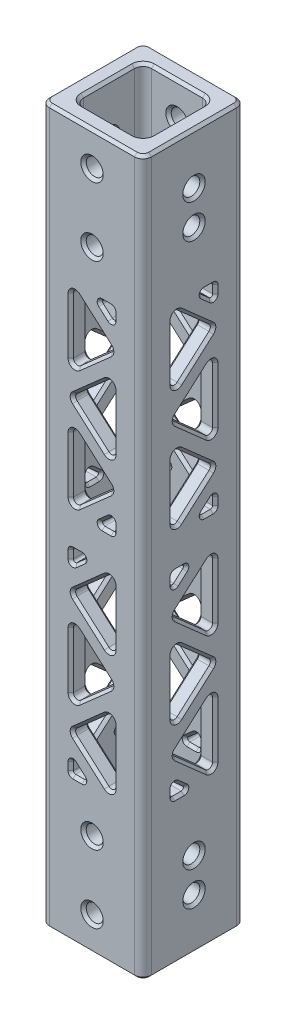
SolidWorks part; units mm, degrees
note: '?' marks a value the reader was unsure of.
ref_plane "Front Plane" through (0, 0, 0) normal (0, 0, 1) x (1, 0, 0)
ref_plane "Top Plane" through (0, 0, 0) normal (0, 1, 0) x (1, 0, 0)
ref_plane "Right Plane" through (0, 0, 0) normal (1, 0, 0) x (0, 0, -1)
sketch "Sketch1" plane through (0, 0, 0) normal (0, 1, 0) x (1, 0, 0)
  line L1 (-9.525, -9.525) -> (9.525, -9.525)
  line L2 (-9.525, -9.525) -> (-9.525, 9.525)
  line L3 (-9.525, 9.525) -> (9.525, 9.525)
  line L4 (9.525, -9.525) -> (9.525, 9.525)
  line L5 (-9.525, -9.525) -> (9.525, 9.525) construction
  line L6 (-9.525, 9.525) -> (9.525, -9.525) construction
  line L7 (-6.35, -6.35) -> (6.35, -6.35)
  line L8 (-6.35, -6.35) -> (-6.35, 6.35)
  line L9 (-6.35, 6.35) -> (6.35, 6.35)
  line L10 (6.35, -6.35) -> (6.35, 6.35)
  line L11 (-6.35, -6.35) -> (6.35, 6.35) construction
  line L12 (-6.35, 6.35) -> (6.35, -6.35) construction
  point P0 (0, 0)
  point P6 (0, 0)
  dimension "D1" = 19.05
  dimension "D2" = 19.05
  dimension "D3" = 12.7
extrude "Boss-Extrude1" add sketch "Sketch1" along normal mid plane 133.35 contours L3 L4 L1 L2
hole_wizard "1/8 (0.125) Diameter Hole1" positions "Sketch8" profile "Sketch9" hole size "1/8" standard "ANSI Inch" end condition through all
sketch "Sketch8" plane through (-9.525, 0, 0) normal (-1, 0, 0) x (0, 0, 1)
  line L2 (0, 57.15) -> (0, 66.675) construction
  line L3 (-9.525, 66.675) -> (9.525, 66.675) construction
  point P0 (0, 57.15)
  point P2 (0, 50.8)
  dimension "D1" = 6.35
  dimension "D2" = 9.525
sketch "Sketch9" plane through (-9.525, 57.15, 0) normal (0, 1, 0) x (0, 0, 1)
  line L0 (0, 0) -> (0, 19.05)
  line L1 (0, 19.05) -> (1.5875, 19.05)
  line L2 (1.5875, 19.05) -> (1.5875, 0)
  line L5 (1.5875, 0) -> (0, 0)
  line L11 (0, -6.35) -> (0, 107.95) construction
  dimension "Thru Hole Dia." = 3.175
  dimension "Thru Hole Depth" = 19.05
hole_wizard "1/8 (0.125) Diameter Hole2" positions "Sketch10" profile "Sketch11" hole size "1/8" standard "ANSI Inch" end condition through all
sketch "Sketch10" plane through (9.525, 0, 0) normal (1, 0, 0) x (0, 0, -1)
  line L0 (0, -66.675) -> (0, -57.15) construction
  line L1 (-9.525, -66.675) -> (9.525, -66.675) construction
  point P0 (0, -50.8)
  point P2 (0, -57.15)
  dimension "D1" = 6.35
  dimension "D2" = 9.525
sketch "Sketch11" plane through (9.525, -50.8, 0) normal (0, 1, 0) x (0, 0, -1)
  line L0 (0, 0) -> (0, 19.05)
  line L1 (0, 19.05) -> (1.5875, 19.05)
  line L2 (1.5875, 19.05) -> (1.5875, 0)
  line L5 (1.5875, 0) -> (0, 0)
  line L11 (0, -6.35) -> (0, 107.95) construction
  dimension "Thru Hole Dia." = 3.175
  dimension "Thru Hole Depth" = 19.05
hole_wizard "1/8 (0.125) Diameter Hole3" positions "Sketch16" profile "Sketch17" hole size "1/8" standard "ANSI Inch" end condition through all
sketch "Sketch16" plane through (0, 0, 9.525) normal (0, 0, 1) x (1, 0, 0)
  line L0 (0, -60.325) -> (0, -66.675) construction
  line L1 (-9.525, -66.675) -> (9.525, -66.675) construction
  line L3 (0, -47.625) -> (0, -60.325) construction
  line L5 (0, 60.325) -> (0, 66.675) construction
  line L6 (-9.525, 66.675) -> (9.525, 66.675) construction
  line L8 (0, 47.625) -> (0, 60.325) construction
  point P0 (0, 60.325)
  point P2 (0, 47.625)
  point P4 (0, -47.625)
  point P6 (0, -60.325)
  dimension "D1" = 6.35
  dimension "D2" = 12.7
sketch "Sketch17" plane through (0, 60.325, 9.525) normal (1, 0, 0) x (0, -1, 0)
  line L0 (0, 0) -> (0, 19.05)
  line L1 (0, 19.05) -> (1.5875, 19.05)
  line L2 (1.5875, 19.05) -> (1.5875, 0)
  line L5 (1.5875, 0) -> (0, 0)
  line L11 (0, -6.35) -> (0, 107.95) construction
  dimension "Thru Hole Dia." = 3.175
  dimension "Thru Hole Depth" = 19.05
sketch "Sketch15" plane through (0, 0, 0) normal (0, 0, 1) x (1, 0, 0)
  line L0 (-3.9687, 39.6875) -> (3.9688, 39.6875) construction
  line L3 (3.9688, 39.6875) -> (3.9687, -39.6875) construction
  line L8 (3.9687, -39.6875) -> (-3.9687, -39.6875) construction
  line L11 (-3.9687, -39.6875) -> (-3.9687, 39.6875) construction
  line L12 (0, -46.0375) -> (0, -39.6875) construction
  line L13 (0, 46.0375) -> (0, 39.6875) construction
  line L23 (-3.9688, 3.175) -> (3.9688, 3.175) construction
  line L24 (-3.9688, -3.175) -> (3.9688, -3.175) construction
  line L28 (0, -3.175) -> (0, 3.175) construction
  line L30 (-3.9687, 39.6875) -> (-0.8276, 39.6875)
  line L31 (-0.8276, 39.6875) -> (-3.9688, 36.9133)
  line L32 (-3.9688, 36.9133) -> (-3.9687, 39.6875)
  line L36 (-3.9688, 32.6774) -> (3.9688, 39.6875)
  line L37 (3.9688, 39.6875) -> (3.9687, 25.6672)
  line L38 (3.9687, 25.6672) -> (-3.9688, 32.6774)
  line L39 (0, 36.1824) -> (-2.1017, 38.5622) construction
  line L45 (-3.9688, 28.4414) -> (3.9688, 21.4313)
  line L49 (3.9688, 21.4313) -> (-3.9688, 14.4211)
  line L53 (-3.9688, 14.4211) -> (-3.9688, 28.4414)
  line L60 (0, 29.1723) -> (-2.1017, 26.7925) construction
  line L64 (-3.9687, 10.1851) -> (3.9687, 17.1953)
  line L68 (3.9687, 17.1953) -> (3.9688, 3.175)
  line L69 (3.9688, 3.175) -> (-3.9687, 10.1851)
  line L70 (0, 13.6902) -> (-2.1017, 16.07) construction
  line L74 (-3.9688, 3.175) -> (-0.8276, 3.175)
  line L78 (-0.8276, 3.175) -> (-3.9688, 5.9492)
  line L88 (0.8276, -3.175) -> (3.9688, -3.175)
  line L89 (-3.9688, -3.175) -> (3.9687, -10.1851)
  line L90 (3.9687, -10.1851) -> (-3.9688, -17.1953)
  line L91 (-3.9688, -17.1953) -> (-3.9688, -3.175)
  line L92 (3.9688, -3.175) -> (3.9687, -5.9492)
  line L93 (-3.9687, -21.4313) -> (3.9688, -14.4211)
  line L94 (3.9688, -14.4211) -> (3.9687, -28.4414)
  line L95 (3.9687, -28.4414) -> (-3.9687, -21.4313)
  line L96 (0, -17.9262) -> (-2.1017, -15.5464) construction
  line L97 (-3.9687, -39.6875) -> (3.9687, -32.6774)
  line L98 (3.9687, -32.6774) -> (-3.9687, -25.6672)
  line L99 (-3.9687, -25.6672) -> (-3.9687, -39.6875)
  line L100 (0, -29.1723) -> (2.1017, -26.7925) construction
  line L101 (0.8276, -39.6875) -> (3.9687, -39.6875)
  line L102 (3.9687, -39.6875) -> (3.9688, -36.9133)
  line L103 (3.9688, -36.9133) -> (0.8276, -39.6875)
  line L104 (2.3982, -38.3004) -> (0.2964, -35.9206) construction
  line L105 (-3.9688, 5.9492) -> (-3.9688, 3.175)
  line L106 (-2.3982, 4.5621) -> (-0.2964, 6.9419) construction
  line L107 (3.9687, -5.9492) -> (0.8276, -3.175)
  line L108 (2.3982, -4.5621) -> (0.2964, -6.9419) construction
  circle A7 centre (0, -47.625) radius 1.5875 construction
  circle A8 centre (0, 47.625) radius 1.5875 construction
  dimension "D3" = 3.175
  dimension "D1" = 7.9375
  dimension "D2" = 6.35
  dimension "D4" = 6.35
extrude "Cut-Extrude1" cut sketch "Sketch15" against normal up to next
ref_axis "Axis2" through (0, -73.3425, 0) along (0, 1, 0)?
pattern_circular "CirPattern2" count 4 over 360 about axis through (0, 0, 0) along (0, 1, 0) of "Cut-Extrude1"
fillet "Fillet1" radius 1.5875 8 edges at (9.525, 0, -9.525) (9.525, 0, 9.525) (-9.525, 0, -9.525) (-9.525, 0, 9.525) (6.35, 0, -6.35) (6.35, 0, 6.35) (-6.35, 0, 6.35) (-6.35, 0, -6.35)
fillet "Fillet2" radius 0.7937 39 edges at (3.9688, -39.6875, 7.9375) (-3.9687, -28.4414, 7.9375) (3.9687, -21.4313, 7.9375) (-3.9688, -14.4211, 7.9375) (3.9688, -17.1953, 7.9375) (-3.9688, 3.175, 7.9375) (3.9688, 28.4414, 7.9375) (-3.9688, 21.4313, 7.9375) (3.9688, 32.6774, 7.9375) (7.9375, -32.6774, 3.9687) (7.9375, -39.6875, -3.9688) (7.9375, -25.6672, -3.9688) (7.9375, -14.4211, 3.9687) (7.9375, -3.175, -3.9688) (7.9375, -10.1851, 3.9687) (7.9375, 3.175, 3.9687) (7.9375, 17.1953, 3.9687) (7.9375, 21.4313, 3.9687) (7.9375, 32.6774, -3.9688) (3.9688, -32.6774, -7.9375) (-3.9687, -25.6672, -7.9375) (3.9687, -28.4414, -7.9375) (-3.9687, -21.4313, -7.9375) (3.9687, -10.1851, -7.9375) (3.9688, 3.175, -7.9375) (-3.9687, 14.4211, -7.9375) (3.9687, 21.4312, -7.9375) (3.9688, 39.6875, -7.9375) (-7.9375, -39.6875, 3.9688) (-7.9375, -25.6672, 3.9688) (-7.9375, -28.4414, -3.9687) (-7.9375, -21.4313, 3.9688) (-7.9375, -10.1851, -3.9687) (-7.9375, 3.175, -3.9687) (-7.9375, 17.1953, -3.9687) (-7.9375, 14.4211, 3.9688) (-7.9375, 21.4313, -3.9687) (-7.9375, 28.4414, 3.9688) (-7.9375, 39.6875, -3.9687)
fillet "Fillet3" radius 0.3969 48 edges at (0.8276, -39.6875, -7.9375) (3.9688, -36.9133, -7.9375) (3.9687, -39.6875, -7.9375) (-3.9688, 36.9133, -7.9375) (-0.8276, 39.6875, -7.9375) (-3.9687, 39.6875, -7.9375) (7.9375, -39.6875, 0.8276) (7.9375, -39.6875, 3.9687) (7.9375, -36.9133, 3.9687) (7.9375, 36.9133, -3.9688) (7.9375, 39.6875, -0.8276) (7.9375, 39.6875, -3.9688) (-0.8276, -39.6875, 7.9375) (-3.9688, -36.9133, 7.9375) (-3.9687, -39.6875, 7.9375) (3.9688, 36.9133, 7.9375) (0.8276, 39.6875, 7.9375) (3.9687, 39.6875, 7.9375) (-7.9375, -39.6875, -0.8276) (-7.9375, -39.6875, -3.9687) (-7.9375, -36.9133, -3.9687) (-7.9375, 36.9133, 3.9688) (-7.9375, 39.6875, 3.9688) (-7.9375, 39.6875, 0.8276) (7.9375, -3.175, 3.9687) (7.9375, -3.175, 0.8276) (7.9375, -5.9492, 3.9687) (7.9375, 3.175, -3.9688) (7.9375, 5.9492, -3.9688) (7.9375, 3.175, -0.8276) (3.9688, -5.9492, -7.9375) (0.8276, -3.175, -7.9375) (3.9688, -3.175, -7.9375) (-3.9688, 3.175, -7.9375) (-3.9688, 5.9492, -7.9375) (-0.8276, 3.175, -7.9375) (-7.9375, 3.175, 0.8276) (-7.9375, 5.9492, 3.9688) (-7.9375, 3.175, 3.9688) (-7.9375, -5.9492, -3.9687) (-7.9375, -3.175, -0.8276) (-7.9375, -3.175, -3.9687) (-3.9688, -3.175, 7.9375) (-0.8276, -3.175, 7.9375) (-3.9687, -5.9492, 7.9375) (0.8276, 3.175, 7.9375) (3.9688, 5.9492, 7.9375) (3.9688, 3.175, 7.9375)
chamfer "Chamfer2" distance 0.508 angle 45 544 edges at (9.525, 3.175, -2.7242) (6.35, 3.175, -2.7242) (9.525, 4.3205, -3.9688) (6.35, 4.3205, -3.9688) (9.525, 4.618, -2.4615) (6.35, 4.618, -2.4615) (3.9688, -4.3205, -9.525) (3.9688, -4.3205, -6.35) (2.4615, -4.618, -9.525) (2.4615, -4.618, -6.35) (2.7242, -3.175, -9.525) (2.7242, -3.175, -6.35) (-2.7242, 3.175, -9.525) (-2.7242, 3.175, -6.35) (-3.9688, 4.3205, -9.525) (-3.9688, 4.3205, -6.35) (-2.4615, 4.618, -9.525) (-2.4615, 4.618, -6.35) (-9.525, 4.618, 2.4615) (-6.35, 4.618, 2.4615) (-9.525, 3.175, 2.7242) (-6.35, 3.175, 2.7242) (-9.525, 4.3205, 3.9688) (-6.35, 4.3205, 3.9688) (-9.525, -4.3205, -3.9687) (-6.35, -4.3205, -3.9687) (-9.525, -4.618, -2.4615) (-6.35, -4.618, -2.4615) (-9.525, -3.175, -2.7242) (-6.35, -3.175, -2.7242) (-2.7242, -3.175, 9.525) (-2.7242, -3.175, 6.35) (-3.9688, -4.3205, 9.525) (-3.9688, -4.3205, 6.35) (-2.4615, -4.618, 9.525) (-2.4615, -4.618, 6.35) (2.4615, 4.618, 9.525) (2.4615, 4.618, 6.35) (2.7242, 3.175, 9.525) (2.7242, 3.175, 6.35) (3.9688, 4.3205, 9.525) (3.9688, 4.3205, 6.35) (2.7242, -39.6875, -9.525) (2.7242, -39.6875, -6.35) (2.4615, -38.2445, -9.525) (2.4615, -38.2445, -6.35) (3.9688, -38.542, -9.525) (3.9688, -38.542, -6.35) (-2.4615, 38.2445, -9.525) (-2.4615, 38.2445, -6.35) (-3.9688, 38.542, -9.525) (-3.9688, 38.542, -6.35) (-2.7242, 39.6875, -9.525) (-2.7242, 39.6875, -6.35) (9.525, -39.6875, 2.7242) (6.35, -39.6875, 2.7242) (9.525, -38.2445, 2.4615) (6.35, -38.2445, 2.4615) (9.525, -38.542, 3.9687) (6.35, -38.542, 3.9687) (9.525, 38.2445, -2.4615) (6.35, 38.2445, -2.4615) (9.525, 38.542, -3.9688) (6.35, 38.542, -3.9688) (9.525, 39.6875, -2.7242) (6.35, 39.6875, -2.7242) (-2.7242, -39.6875, 9.525) (-2.7242, -39.6875, 6.35) (-2.4615, -38.2445, 9.525) (-2.4615, -38.2445, 6.35) (-3.9688, -38.542, 9.525) (-3.9688, -38.542, 6.35) (2.4615, 38.2445, 9.525) (2.4615, 38.2445, 6.35) (3.9688, 38.542, 9.525) (3.9688, 38.542, 6.35) (2.7242, 39.6875, 9.525) (2.7242, 39.6875, 6.35) (-9.525, -39.6875, -2.7242) (-6.35, -39.6875, -2.7242) (-9.525, -38.2445, -2.4615) (-6.35, -38.2445, -2.4615) (-9.525, -38.542, -3.9687) (-6.35, -38.542, -3.9687) (-9.525, 38.2445, 2.4615) (-6.35, 38.2445, 2.4615) (-9.525, 38.542, 3.9688) (-6.35, 38.542, 3.9688) (-9.525, 39.6875, 2.7242) (-6.35, 39.6875, 2.7242) (6.35, -3.2912, 3.8525) (9.525, -3.2912, 3.8525) (6.35, -3.4314, 1.5053) (9.525, -3.4314, 1.5053) (6.35, -5.431, 3.735) (9.525, -5.431, 3.735) (6.35, 3.2912, -3.8525) (9.525, 3.2912, -3.8525) (6.35, 5.431, -3.735) (9.525, 5.431, -3.735) (6.35, 3.4314, -1.5053) (9.525, 3.4314, -1.5053) (3.735, -5.431, -6.35) (3.735, -5.431, -9.525) (1.5053, -3.4314, -6.35) (1.5053, -3.4314, -9.525) (3.8525, -3.2912, -6.35) (3.8525, -3.2912, -9.525) (-3.8525, 3.2912, -6.35) (-3.8525, 3.2912, -9.525) (-3.735, 5.431, -6.35) (-3.735, 5.431, -9.525) (-1.5053, 3.4314, -6.35) (-1.5053, 3.4314, -9.525) (-6.35, 3.4314, 1.5053) (-9.525, 3.4314, 1.5053) (-6.35, 5.431, 3.735) (-9.525, 5.431, 3.735) (-6.35, 3.2912, 3.8525) (-9.525, 3.2912, 3.8525) (-6.35, -5.431, -3.735) (-9.525, -5.431, -3.735) (-6.35, -3.4314, -1.5053) (-9.525, -3.4314, -1.5053) (-6.35, -3.2912, -3.8525) (-9.525, -3.2912, -3.8525) (-3.8525, -3.2912, 6.35) (-3.8525, -3.2912, 9.525) (-1.5053, -3.4314, 6.35) (-1.5053, -3.4314, 9.525) (-3.735, -5.431, 6.35) (-3.735, -5.431, 9.525) (1.5053, 3.4314, 6.35) (1.5053, 3.4314, 9.525) (3.735, 5.431, 6.35) (3.735, 5.431, 9.525) (3.8525, 3.2912, 6.35) (3.8525, 3.2912, 9.525) (1.5053, -39.4311, -6.35) (1.5053, -39.4311, -9.525) (3.735, -37.4315, -6.35) (3.735, -37.4315, -9.525) (3.8525, -39.5713, -6.35) (3.8525, -39.5713, -9.525) (-3.735, 37.4315, -6.35) (-3.735, 37.4315, -9.525) (-1.5053, 39.4311, -6.35) (-1.5053, 39.4311, -9.525) (-3.8525, 39.5713, -6.35) (-3.8525, 39.5713, -9.525) (6.35, -39.4311, 1.5053) (9.525, -39.4311, 1.5053) (6.35, -39.5713, 3.8525) (9.525, -39.5713, 3.8525) (6.35, -37.4315, 3.735) (9.525, -37.4315, 3.735) (6.35, 37.4315, -3.735) (9.525, 37.4315, -3.735) (6.35, 39.4311, -1.5053) (9.525, 39.4311, -1.5053) (6.35, 39.5713, -3.8525) (9.525, 39.5713, -3.8525) (-1.5053, -39.4311, 6.35) (-1.5053, -39.4311, 9.525) (-3.735, -37.4315, 6.35) (-3.735, -37.4315, 9.525) (-3.8525, -39.5713, 6.35) (-3.8525, -39.5713, 9.525) (3.735, 37.4315, 6.35) (3.735, 37.4315, 9.525) (1.5053, 39.4311, 6.35) (1.5053, 39.4311, 9.525) (3.8525, 39.5713, 6.35) (3.8525, 39.5713, 9.525) (-6.35, -39.4311, -1.5053) (-9.525, -39.4311, -1.5053) (-6.35, -39.5713, -3.8525) (-9.525, -39.5713, -3.8525) (-6.35, -37.4315, -3.735) (-9.525, -37.4315, -3.735) (-6.35, 37.4315, 3.735) (-9.525, 37.4315, 3.735) (-6.35, 39.5713, 3.8525) (-9.525, 39.5713, 3.8525) (-6.35, 39.4311, 1.5053) (-9.525, 39.4311, 1.5053) (-6.35, 50.8, -1.5875) (6.35, 50.8, 1.5875) (9.525, 50.8, 1.5875) (-9.525, 50.8, 1.5875) (6.35, 57.15, 1.5875) (-6.35, 57.15, -1.5875) (-9.525, 57.15, 1.5875) (9.525, 57.15, 1.5875) (0, -66.675, -9.525) (0, 66.675, -9.525) (9.525, -66.675, 0) (0, -66.675, 9.525) (-9.525, -66.675, 0) (0, -66.675, 6.35) (6.35, -66.675, 0) (6.35, -57.15, 1.5875) (0, -66.675, -6.35) (-6.35, -57.15, -1.5875) (-6.35, -66.675, 0) (-9.06, -66.675, 9.06) (-9.525, -57.15, -1.5875) (-9.06, -66.675, -9.06) (9.06, -66.675, 9.06) (9.525, -57.15, -1.5875) (9.06, -66.675, -9.06) (9.525, 66.675, 0) (-9.525, 66.675, 0) (0, 66.675, 9.525) (6.35, 66.675, 0) (0, 66.675, 6.35) (-6.35, 66.675, 0) (0, 66.675, -6.35) (-9.06, 66.675, 9.06) (-9.06, 66.675, -9.06) (9.06, 66.675, 9.06) (9.06, 66.675, -9.06) (5.885, -66.675, -5.885) (5.885, 66.675, -5.885) (5.885, -66.675, 5.885) (5.885, 66.675, 5.885) (-5.885, -66.675, 5.885) (-5.885, 66.675, 5.885) (-5.885, -66.675, -5.885) (-5.885, 66.675, -5.885) (-0.3228, -35.8974, 9.525) (-0.3228, -35.8974, 6.35) (3.9687, -32.6774, 9.525) (3.9687, -32.6774, 6.35) (-0.3228, -29.4573, 9.525) (-0.3228, -29.4573, 6.35) (-3.9688, -21.4313, 9.525) (-3.9688, -21.4313, 6.35) (0.3228, -24.6513, 9.525) (0.3228, -24.6513, 6.35) (0.3228, -18.2112, 9.525) (0.3228, -18.2112, 6.35) (-0.3228, -13.4052, 9.525) (-0.3228, -13.4052, 6.35) (3.9688, -10.1851, 9.525) (3.9688, -10.1851, 6.35) (-0.3228, -6.9651, 9.525) (-0.3228, -6.9651, 6.35) (-3.9688, 10.1851, 9.525) (-3.9688, 10.1851, 6.35) (0.3228, 6.9651, 9.525) (0.3228, 6.9651, 6.35) (0.3228, 13.4052, 9.525) (0.3228, 13.4052, 6.35) (-0.3228, 18.2112, 9.525) (-0.3228, 18.2112, 6.35) (-6.35, -50.8, -1.5875) (6.35, -50.8, 1.5875) (3.9688, 21.4312, 9.525) (9.525, -50.8, -1.5875) (3.9688, 21.4312, 6.35) (-9.525, -50.8, -1.5875) (-0.3228, 24.6513, 9.525) (-0.3228, 24.6513, 6.35) (-3.9688, 32.6774, 9.525) (-3.9688, 32.6774, 6.35) (0.3228, 29.4573, 9.525) (0.3228, 29.4573, 6.35) (0.3228, 35.8974, 9.525) (0.3228, 35.8974, 6.35) (9.525, -29.4573, 0.3228) (6.35, -29.4573, 0.3228) (9.525, -35.8974, 0.3228) (6.35, -35.8974, 0.3228) (9.525, -32.6774, -3.9688) (6.35, -32.6774, -3.9688) (9.525, -21.4313, 3.9687) (6.35, -21.4313, 3.9687) (9.525, -24.6513, -0.3228) (6.35, -24.6513, -0.3228) (9.525, -18.2112, -0.3228) (6.35, -18.2112, -0.3228) (9.525, -13.4052, 0.3228) (6.35, -13.4052, 0.3228) (9.525, -10.1851, -3.9688) (6.35, -10.1851, -3.9688) (9.525, -6.9651, 0.3228) (6.35, -6.9651, 0.3228) (9.525, 10.1851, 3.9687) (6.35, 10.1851, 3.9687) (9.525, 6.9651, -0.3228) (6.35, 6.9651, -0.3228) (9.525, 13.4052, -0.3228) (6.35, 13.4052, -0.3228) (9.525, 18.2112, 0.3228) (6.35, 18.2112, 0.3228) (9.525, 21.4312, -3.9688) (6.35, 21.4312, -3.9688) (9.525, 24.6513, 0.3228) (6.35, 24.6513, 0.3228) (9.525, 32.6774, 3.9687) (6.35, 32.6774, 3.9687) (9.525, 29.4573, -0.3228) (6.35, 29.4573, -0.3228) (9.525, 35.8974, -0.3228) (6.35, 35.8974, -0.3228) (0.3228, -35.8974, -9.525) (0.3228, -35.8974, -6.35) (-3.9687, -32.6774, -9.525) (-3.9687, -32.6774, -6.35) (0.3228, -29.4573, -9.525) (0.3228, -29.4573, -6.35) (3.9688, -21.4313, -9.525) (3.9688, -21.4313, -6.35) (-0.3228, -24.6513, -9.525) (-0.3228, -24.6513, -6.35) (-0.3228, -18.2112, -9.525) (-0.3228, -18.2112, -6.35) (0.3228, -13.4052, -9.525) (0.3228, -13.4052, -6.35) (-3.9688, -10.1851, -9.525) (-3.9688, -10.1851, -6.35) (0.3228, -6.9651, -9.525) (0.3228, -6.9651, -6.35) (3.9688, 10.1851, -9.525) (3.9688, 10.1851, -6.35) (-0.3228, 6.9651, -9.525) (-0.3228, 6.9651, -6.35) (-0.3228, 13.4052, -9.525) (-0.3228, 13.4052, -6.35) (0.3228, 18.2112, -9.525) (0.3228, 18.2112, -6.35) (-3.9688, 21.4312, -9.525) (-3.9688, 21.4312, -6.35) (0.3228, 24.6513, -9.525) (0.3228, 24.6513, -6.35) (3.9688, 32.6774, -9.525) (3.9688, 32.6774, -6.35) (-0.3228, 29.4573, -9.525) (-0.3228, 29.4573, -6.35) (-0.3228, 35.8974, -9.525) (-0.3228, 35.8974, -6.35) (-9.525, -35.8974, -0.3228) (-6.35, -35.8974, -0.3228) (-9.525, -32.6774, 3.9688) (-6.35, -32.6774, 3.9688) (-9.525, -29.4573, -0.3228) (-6.35, -29.4573, -0.3228) (-9.525, -21.4313, -3.9687) (-6.35, -21.4313, -3.9687) (-9.525, -24.6513, 0.3228) (-6.35, -24.6513, 0.3228) (-9.525, -18.2112, 0.3228) (-6.35, -18.2112, 0.3228) (-9.525, -13.4052, -0.3228) (-6.35, -13.4052, -0.3228) (-9.525, -10.1851, 3.9688) (-6.35, -10.1851, 3.9688) (-9.525, -6.9651, -0.3228) (-6.35, -6.9651, -0.3228) (-9.525, 10.1851, -3.9687) (-6.35, 10.1851, -3.9687) (-9.525, 6.9651, 0.3228) (-6.35, 6.9651, 0.3228) (-9.525, 13.4052, 0.3228) (-6.35, 13.4052, 0.3228) (-9.525, 18.2112, -0.3228) (-6.35, 18.2112, -0.3228) (-9.525, 21.4312, 3.9688) (-6.35, 21.4312, 3.9688) (-9.525, 24.6513, -0.3228) (-1.5875, -60.325, 6.35) (-6.35, 24.6513, -0.3228) (1.5875, -60.325, -6.35) (-9.525, 29.4573, 0.3228) (1.5875, -60.325, -9.525) (-6.35, 29.4573, 0.3228) (1.5875, -60.325, 9.525) (-9.525, 35.8974, 0.3228) (-6.35, 35.8974, 0.3228) (-9.525, 32.6774, -3.9687) (-6.35, 32.6774, -3.9687) (3.5013, -38.6511, 6.35) (3.5013, -38.6511, 9.525) (3.5013, -26.7036, 6.35) (3.5013, -26.7036, 9.525) (-3.5634, -32.6774, 6.35) (-3.5634, -32.6774, 9.525) (-3.5013, -27.405, 6.35) (-3.5013, -27.405, 9.525) (3.5634, -21.4313, 6.35) (3.5634, -21.4313, 9.525) (-3.5013, -15.4575, 6.35) (-3.5013, -15.4575, 9.525) (3.5013, -16.1589, 6.35) (3.5013, -16.1589, 9.525) (3.5013, -4.2114, 6.35) (3.5013, -4.2114, 9.525) (-3.5634, -10.1851, 6.35) (-3.5634, -10.1851, 9.525) (-3.5013, 4.2114, 6.35) (-3.5013, 4.2114, 9.525) (3.5634, 10.1851, 6.35) (3.5634, 10.1851, 9.525) (-3.5013, 16.1589, 6.35) (-3.5013, 16.1589, 9.525) (3.5013, 15.4575, 6.35) (3.5013, 15.4575, 9.525) (3.5013, 27.405, 6.35) (3.5013, 27.405, 9.525) (-3.5634, 21.4313, 6.35) (-3.5634, 21.4313, 9.525) (-3.5013, 26.7036, 6.35) (-3.5013, 26.7036, 9.525) (3.5634, 32.6774, 6.35) (3.5634, 32.6774, 9.525) (-3.5013, 38.6511, 6.35) (-3.5013, 38.6511, 9.525) (6.35, -32.6774, 3.5634) (9.525, -32.6774, 3.5634) (6.35, -38.6511, -3.5013) (9.525, -38.6511, -3.5013) (6.35, -26.7036, -3.5013) (9.525, -26.7036, -3.5013) (6.35, -27.405, 3.5013) (9.525, -27.405, 3.5013) (6.35, -15.4575, 3.5013) (9.525, -15.4575, 3.5013) (6.35, -21.4313, -3.5634) (9.525, -21.4313, -3.5634) (6.35, -16.1589, -3.5013) (9.525, -16.1589, -3.5013) (6.35, -4.2114, -3.5013) (9.525, -4.2114, -3.5013) (6.35, -10.1851, 3.5634) (9.525, -10.1851, 3.5634) (6.35, 4.2114, 3.5013) (9.525, 4.2114, 3.5013) (6.35, 16.1589, 3.5013) (9.525, 16.1589, 3.5013) (6.35, 10.1851, -3.5634) (9.525, 10.1851, -3.5634) (6.35, 15.4575, -3.5013) (9.525, 15.4575, -3.5013) (6.35, 27.405, -3.5013) (9.525, 27.405, -3.5013) (6.35, 21.4313, 3.5634) (9.525, 21.4313, 3.5634) (6.35, 26.7036, 3.5013) (9.525, 26.7036, 3.5013) (6.35, 32.6774, -3.5634) (9.525, 32.6774, -3.5634) (6.35, 38.6511, 3.5013) (9.525, 38.6511, 3.5013) (-3.5013, -38.6511, -6.35) (-3.5013, -38.6511, -9.525) (3.5634, -32.6774, -6.35) (3.5634, -32.6774, -9.525) (-3.5013, -26.7036, -6.35) (-3.5013, -26.7036, -9.525) (3.5013, -27.405, -6.35) (3.5013, -27.405, -9.525) (3.5013, -15.4575, -6.35) (3.5013, -15.4575, -9.525) (-3.5634, -21.4313, -6.35) (-3.5634, -21.4313, -9.525) (-3.5013, -16.1589, -6.35) (-3.5013, -16.1589, -9.525) (-3.5013, -4.2114, -6.35) (-3.5013, -4.2114, -9.525) (3.5634, -10.1851, -6.35) (3.5634, -10.1851, -9.525) (3.5013, 4.2114, -6.35) (3.5013, 4.2114, -9.525) (-3.5634, 10.1851, -6.35) (-3.5634, 10.1851, -9.525) (3.5013, 16.1589, -6.35) (3.5013, 16.1589, -9.525) (-3.5013, 15.4575, -6.35) (-3.5013, 15.4575, -9.525) (-3.5013, 27.405, -6.35) (-3.5013, 27.405, -9.525) (3.5634, 21.4313, -6.35) (3.5634, 21.4313, -9.525) (3.5013, 26.7036, -6.35) (3.5013, 26.7036, -9.525) (-3.5634, 32.6774, -6.35) (-3.5634, 32.6774, -9.525) (3.5013, 38.6511, -6.35) (3.5013, 38.6511, -9.525) (-6.35, -38.6511, 3.5013) (-9.525, -38.6511, 3.5013) (-6.35, -26.7036, 3.5013) (-9.525, -26.7036, 3.5013) (-6.35, -32.6774, -3.5634) (-9.525, -32.6774, -3.5634) (-6.35, -27.405, -3.5013) (-9.525, -27.405, -3.5013) (-6.35, -15.4575, -3.5013) (-9.525, -15.4575, -3.5013) (-6.35, -21.4312, 3.5634) (-9.525, -21.4312, 3.5634) (-6.35, -16.1589, 3.5013) (-9.525, -16.1589, 3.5013) (-6.35, -10.1851, -3.5634) (-9.525, -10.1851, -3.5634) (-6.35, -4.2114, 3.5013) (-9.525, -4.2114, 3.5013) (-6.35, 4.2114, -3.5013) (-9.525, 4.2114, -3.5013) (-6.35, 16.1589, -3.5013) (-9.525, 16.1589, -3.5013) (-6.35, 10.1851, 3.5634) (-9.525, 10.1851, 3.5634) (-6.35, 15.4575, 3.5013) (-9.525, 15.4575, 3.5013) (-6.35, 21.4313, -3.5634) (-9.525, 21.4313, -3.5634) (-6.35, 27.405, 3.5013) (-9.525, 27.405, 3.5013) (-6.35, 32.6774, 3.5634) (-9.525, 32.6774, 3.5634) (-6.35, 26.7036, -3.5013) (-9.525, 26.7036, -3.5013) (-6.35, 38.6511, -3.5013) (-9.525, 38.6511, -3.5013) (1.5875, -47.625, -6.35) (-1.5875, -47.625, 6.35) (1.5875, -47.625, 9.525) (1.5875, -47.625, -9.525) (-1.5875, 47.625, 6.35) (1.5875, 47.625, -6.35) (1.5875, 47.625, -9.525) (1.5875, 47.625, 9.525) (-1.5875, 60.325, 6.35) (1.5875, 60.325, -6.35) (1.5875, 60.325, -9.525) (1.5875, 60.325, 9.525) (9.525, -3.175, 2.7242) (6.35, -3.175, 2.7242) (9.525, -4.3205, 3.9687) (6.35, -4.3205, 3.9687) (9.525, -4.618, 2.4615) (6.35, -4.618, 2.4615)
equation "\"D2@Sketch1\"=\"D1@Sketch1\""
